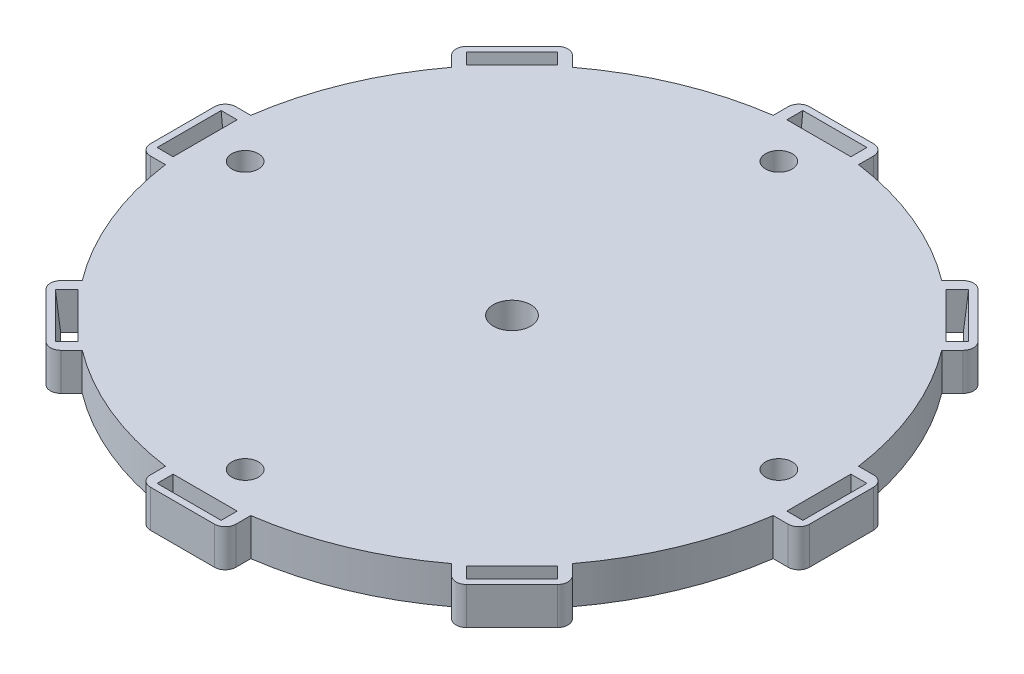
SolidWorks part; units mm, degrees
ref_plane "Front Plane" through (0, 0, 0) normal (0, 0, 1) x (1, 0, 0)
ref_plane "Top Plane" through (0, 0, 0) normal (0, 1, 0) x (1, 0, 0)
ref_plane "Right Plane" through (0, 0, 0) normal (1, 0, 0) x (0, 0, -1)
sketch "Sketch1" plane through (0, 0, 0) normal (0, 1, 0) x (1, 0, 0)
  line L0 (-8, 56.9408) -> (-8, 59.7408)
  line L1 (0, 57.5) -> (0, -57.5) construction
  line L2 (8, 56.9408) -> (8, 59.7408)
  line L3 (-6, 61.7408) -> (6, 61.7408)
  line L4 (39.4147, 47.8999) -> (47.8999, 39.4147)
  line L9 (34.6063, 45.9201) -> (36.5862, 47.8999)
  line L10 (45.9201, 34.6063) -> (47.8999, 36.5862)
  line L15 (61.7408, 6) -> (61.7408, -6)
  line L16 (56.9408, 8) -> (59.7408, 8)
  line L17 (56.9408, -8) -> (59.7408, -8)
  line L22 (47.8999, -39.4147) -> (39.4147, -47.8999)
  line L23 (45.9201, -34.6063) -> (47.8999, -36.5862)
  line L24 (34.6063, -45.9201) -> (36.5862, -47.8999)
  line L29 (6, -61.7408) -> (-6, -61.7408)
  line L30 (8, -56.9408) -> (8, -59.7408)
  line L31 (-8, -56.9408) -> (-8, -59.7408)
  line L36 (-39.4147, -47.8999) -> (-47.8999, -39.4147)
  line L37 (-34.6063, -45.9201) -> (-36.5862, -47.8999)
  line L38 (-45.9201, -34.6063) -> (-47.8999, -36.5862)
  line L43 (-61.7408, -6) -> (-61.7408, 6)
  line L44 (-56.9408, -8) -> (-59.7408, -8)
  line L45 (-56.9408, 8) -> (-59.7408, 8)
  line L50 (-47.8999, 39.4147) -> (-39.4147, 47.8999)
  line L51 (-45.9201, 34.6063) -> (-47.8999, 36.5862)
  line L52 (-34.6063, 45.9201) -> (-36.5862, 47.8999)
  arc A0 (-8, 56.9408) -> (-34.6063, 45.9201) centre (0, 0) ccw
  arc A1 (6, 61.7408) -> (8, 59.7408) centre (6, 59.7408) cw
  arc A2 (-6, 61.7408) -> (-8, 59.7408) centre (-6, 59.7408) ccw
  arc A3 (39.4147, 47.8999) -> (36.5862, 47.8999) centre (38.0005, 46.4857) ccw
  arc A4 (47.8999, 39.4147) -> (47.8999, 36.5862) centre (46.4857, 38.0005) cw
  arc A5 (61.7408, 6) -> (59.7408, 8) centre (59.7408, 6) ccw
  arc A6 (61.7408, -6) -> (59.7408, -8) centre (59.7408, -6) cw
  arc A7 (47.8999, -39.4147) -> (47.8999, -36.5862) centre (46.4857, -38.0005) ccw
  arc A8 (39.4147, -47.8999) -> (36.5862, -47.8999) centre (38.0005, -46.4857) cw
  arc A9 (6, -61.7408) -> (8, -59.7408) centre (6, -59.7408) ccw
  arc A10 (-6, -61.7408) -> (-8, -59.7408) centre (-6, -59.7408) cw
  arc A11 (-39.4147, -47.8999) -> (-36.5862, -47.8999) centre (-38.0005, -46.4857) ccw
  arc A12 (-47.8999, -39.4147) -> (-47.8999, -36.5862) centre (-46.4857, -38.0005) cw
  arc A13 (-61.7408, -6) -> (-59.7408, -8) centre (-59.7408, -6) ccw
  arc A14 (-61.7408, 6) -> (-59.7408, 8) centre (-59.7408, 6) cw
  arc A15 (-47.8999, 39.4147) -> (-47.8999, 36.5862) centre (-46.4857, 38.0005) ccw
  arc A16 (-39.4147, 47.8999) -> (-36.5862, 47.8999) centre (-38.0005, 46.4857) cw
  arc A17 (-45.9201, 34.6063) -> (-56.9408, 8) centre (0, 0) ccw
  arc A18 (-56.9408, -8) -> (-45.9201, -34.6063) centre (0, 0) ccw
  arc A19 (34.6063, 45.9201) -> (8, 56.9408) centre (0, 0) ccw
  arc A20 (-34.6063, -45.9201) -> (-8, -56.9408) centre (0, 0) ccw
  arc A21 (8, -56.9408) -> (34.6063, -45.9201) centre (0, 0) ccw
  arc A22 (45.9201, -34.6063) -> (56.9408, -8) centre (0, 0) ccw
  arc A23 (56.9408, 8) -> (45.9201, 34.6063) centre (0, 0) ccw
  point P11 (8, 61.7408)
  point P14 (-8, 61.7408)
  point P17 (-8, 58.3408)
  point P98 (0, 0)
  dimension "D1" = 115
  dimension "D2" = 2
  dimension "D3" = 16
  dimension "D4" = 2.8
  dimension "D7" = 8
extrude "Boss-Extrude1" add sketch "Sketch1" along normal blind 7
sketch "Sketch2" plane through (0, 7, 0) normal (0, 1, 0) x (1, 0, 0)
  line L0 (-57.5, 0) -> (57.5, 0) construction
  line L1 (0, 0) -> (0, 10) construction
  line L7 (17, 5) -> (22, 5)
  line L14 (0, 10) -> (29.7122, 10) construction
  line L15 (0, 10) -> (-19.5, 10) construction
  line L17 (17, 5) -> (17, 15)
  line L18 (-22, 15) -> (-17, 15)
  line L19 (-22, 15) -> (-22, 5)
  line L20 (-22, 5) -> (-17, 5)
  line L21 (-17, 15) -> (-17, 5)
  line L22 (-22, 15) -> (-17, 5) construction
  line L23 (-22, 5) -> (-17, 15) construction
  line L24 (17, 15) -> (22, 15)
  line L25 (22, 5) -> (22, 15)
  line L26 (17, 5) -> (22, 15) construction
  line L27 (17, 15) -> (22, 5) construction
  circle A0 centre (0, 0) radius 57.5 construction
  point P8 (19.5, 10)
  dimension "D1" = 10
  dimension "D2" = 17
  dimension "D3" = 17
  dimension "D4" = 10
  dimension "D5" = 5
  dimension "D6" = 10
  dimension "D7" = 5
extrude "Boss-Extrude2" add sketch "Sketch2" along normal blind 95
sketch "Sketch15" plane through (0, 0, 0) normal (0, -1, 0) x (1, 0, 0)
  circle A0 centre (0, 0) radius 3.5
  dimension "D1" = 7
extrude "Cut-Extrude3" cut sketch "Sketch15" along direction (0, 1, 0) on the side against the normal up to surface (7 mm away) contours A0 up to face at (0, 7, 0)
sketch "Sketch16" plane through (0, 0, 0) normal (0, -1, 0) x (1, 0, 0)
  line L1 (-6, 59.8) -> (6, 59.8)
  line L2 (-6, 59.8) -> (-6, 57.5)
  line L3 (-6, 57.5) -> (6, 57.5)
  line L4 (6, 59.8) -> (6, 57.5)
  point P5 (0, 57.5)
  dimension "D1" = 2.3
  dimension "D2" = 12
  dimension "D3" = 57.5
sketch "Sketch17" plane through (0, 7, 0) normal (0, 1, 0) x (1, 0, 0)
  line L0 (-6, -57.5) -> (6, -57.5) construction
  line L1 (-6, -57.5) -> (6, -57.5)
  line L2 (-6, -57.5) -> (-6, -60.5)
  line L3 (-6, -60.5) -> (6, -60.5)
  line L4 (6, -60.5) -> (6, -57.5)
  dimension "D1" = 3
ref_axis "Axis1" through (0, 107.1, 0) along (0, -1, 0)
loft "Cut-Loft2" cut profiles "Sketch16", "Sketch17" connector at (6, 0, 59.8) connector at (6, 7, 60.5)
pattern_circular "CirPattern1" count 8 over 360 about axis through (0, 107.1, 0) along (0, -1, 0) of "Cut-Loft2"
sketch "Sketch18" plane through (-17, 0, 0) normal (1, 0, 0) x (0, 0, -1)
  line L0 (15, 102) -> (15, 7) construction
  line L1 (5, 102) -> (15, 102)
  line L2 (5, 102) -> (5, 97)
  line L3 (5, 97) -> (15, 97)
  line L4 (15, 102) -> (15, 97)
  dimension "D1" = 5
extrude "Boss-Extrude3" add sketch "Sketch18" along normal up to surface (34 mm away) up to face at (17, 54.5, -10)
sketch "Sketch19" plane through (0, 0, -15) normal (0, 0, -1) x (-1, 0, 0)
  line L0 (-17, 93) -> (-11.0447, 92.2688)
  line L1 (-17, 97) -> (-17, 7) construction
  line L4 (-11, 91) -> (-19.8185, 91) construction
  line L5 (-17, 89) -> (-11.0447, 89.7312)
  line L6 (-17, 93) -> (-17, 89)
  arc A1 (-11.0447, 92.2688) -> (-11.0447, 89.7312) centre (-11.2005, 91) cw
  dimension "D1" = 6
  dimension "D4" = 4
  dimension "D2" = 7
  dimension "D3" = 4
extrude "Boss-Extrude4" add sketch "Sketch19" against normal blind 10
fillet "Fillet1" radius 2 2 edges at (17, 93, -10) (17, 89, -10)
fillet "Fillet2" radius 2 4 edges at (-22, 102, -10) (22, 102, -10) (-17, 97, -10) (17, 97, -10)
pattern_linear "LPattern2" count 10 spacing 8 along (0, -1, 0) of "Fillet1", "Boss-Extrude4"
sketch "Sketch20" plane through (0, 7, 0) normal (0, 1, 0) x (1, 0, 0)
  line L0 (0, 0) -> (0, 50) construction
  circle A0 centre (0, 50) radius 2.5
  dimension "D2" = 5
  dimension "D1" = 50
extrude "Cut-Extrude4" cut sketch "Sketch20" against normal blind 10
pattern_circular "CirPattern2" count 4 over 360 about axis through (0, 107.1, 0) along (0, -1, 0) of "Cut-Extrude4"
sketch "Sketch22" plane through (0, 0, -15) normal (0, 0, -1) x (-1, 0, 0)
  line L38 (20, 102) -> (-20, 102)
  line L39 (-22, 100) -> (-22, 7)
  line L40 (-22, 7) -> (-17, 7)
  line L41 (-17, 7) -> (-17, 15.2305)
  line L42 (-15.2437, 17.2156) -> (-11.0447, 17.7312)
  line L43 (-11.0447, 20.2688) -> (-15.2437, 20.7844)
  line L44 (-17, 22.7695) -> (-17, 23.2305)
  line L45 (-15.2437, 25.2156) -> (-11.0447, 25.7312)
  line L46 (-11.0447, 28.2688) -> (-15.2437, 28.7844)
  line L47 (-17, 30.7695) -> (-17, 31.2305)
  line L48 (-15.2437, 33.2156) -> (-11.0447, 33.7312)
  line L49 (-11.0447, 36.2688) -> (-15.2437, 36.7844)
  line L50 (-17, 38.7695) -> (-17, 39.2305)
  line L51 (-15.2437, 41.2156) -> (-11.0447, 41.7312)
  line L52 (-11.0447, 44.2688) -> (-15.2437, 44.7844)
  line L53 (-17, 46.7695) -> (-17, 47.2305)
  line L54 (-15.2437, 49.2156) -> (-11.0447, 49.7312)
  line L55 (-11.0447, 52.2688) -> (-15.2437, 52.7844)
  line L56 (-17, 54.7695) -> (-17, 55.2305)
  line L57 (-15.2437, 57.2156) -> (-11.0447, 57.7312)
  line L58 (-11.0447, 60.2688) -> (-15.2437, 60.7844)
  line L59 (-17, 62.7695) -> (-17, 63.2305)
  line L60 (-15.2437, 65.2156) -> (-11.0447, 65.7312)
  line L61 (-11.0447, 68.2688) -> (-15.2437, 68.7844)
  line L62 (-17, 70.7695) -> (-17, 71.2305)
  line L63 (-15.2437, 73.2156) -> (-11.0447, 73.7312)
  line L64 (-11.0447, 76.2688) -> (-15.2437, 76.7844)
  line L65 (-17, 78.7695) -> (-17, 79.2305)
  line L66 (-15.2437, 81.2156) -> (-11.0447, 81.7312)
  line L67 (-11.0447, 84.2688) -> (-15.2437, 84.7844)
  line L68 (-17, 86.7695) -> (-17, 87.2305)
  line L69 (-15.2437, 89.2156) -> (-11.0447, 89.7312)
  line L70 (-11.0447, 92.2688) -> (-15.2437, 92.7844)
  line L71 (-17, 94.7695) -> (-17, 95)
  line L72 (-15, 97) -> (15, 97)
  line L73 (17, 95) -> (17, 7)
  line L74 (17, 7) -> (22, 7)
  line L75 (22, 7) -> (22, 100)
  line L76 (20, 102) -> (-20, 102)
  line L77 (-22, 100) -> (-22, 7)
  line L78 (-22, 7) -> (-17, 7)
  line L79 (-17, 7) -> (-17, 15.2305)
  line L80 (-15.2437, 17.2156) -> (-11.0447, 17.7312)
  line L81 (-11.0447, 20.2688) -> (-15.2437, 20.7844)
  line L82 (-17, 22.7695) -> (-17, 23.2305)
  line L83 (-15.2437, 25.2156) -> (-11.0447, 25.7312)
  line L84 (-11.0447, 28.2688) -> (-15.2437, 28.7844)
  line L85 (-17, 30.7695) -> (-17, 31.2305)
  line L86 (-15.2437, 33.2156) -> (-11.0447, 33.7312)
  line L87 (-11.0447, 36.2688) -> (-15.2437, 36.7844)
  line L88 (-17, 38.7695) -> (-17, 39.2305)
  line L89 (-15.2437, 41.2156) -> (-11.0447, 41.7312)
  line L90 (-11.0447, 44.2688) -> (-15.2437, 44.7844)
  line L91 (-17, 46.7695) -> (-17, 47.2305)
  line L92 (-15.2437, 49.2156) -> (-11.0447, 49.7312)
  line L93 (-11.0447, 52.2688) -> (-15.2437, 52.7844)
  line L94 (-17, 54.7695) -> (-17, 55.2305)
  line L95 (-15.2437, 57.2156) -> (-11.0447, 57.7312)
  line L96 (-11.0447, 60.2688) -> (-15.2437, 60.7844)
  line L97 (-17, 62.7695) -> (-17, 63.2305)
  line L98 (-15.2437, 65.2156) -> (-11.0447, 65.7312)
  line L99 (-11.0447, 68.2688) -> (-15.2437, 68.7844)
  line L100 (-17, 70.7695) -> (-17, 71.2305)
  line L101 (-15.2437, 73.2156) -> (-11.0447, 73.7312)
  line L102 (-11.0447, 76.2688) -> (-15.2437, 76.7844)
  line L103 (-17, 78.7695) -> (-17, 79.2305)
  line L104 (-15.2437, 81.2156) -> (-11.0447, 81.7312)
  line L105 (-11.0447, 84.2688) -> (-15.2437, 84.7844)
  line L106 (-17, 86.7695) -> (-17, 87.2305)
  line L107 (-15.2437, 89.2156) -> (-11.0447, 89.7312)
  line L108 (-11.0447, 92.2688) -> (-15.2437, 92.7844)
  line L109 (-17, 94.7695) -> (-17, 95)
  line L110 (-15, 97) -> (15, 97)
  line L111 (17, 95) -> (17, 7)
  line L112 (17, 7) -> (22, 7)
  line L113 (22, 7) -> (22, 100)
  arc A34 (-20, 102) -> (-22, 100) centre (-20, 100) ccw
  arc A35 (-15.2437, 17.2156) -> (-17, 15.2305) centre (-15, 15.2305) ccw
  arc A36 (-11.0447, 17.7312) -> (-11.0447, 20.2688) centre (-11.2005, 19) ccw
  arc A37 (-17, 22.7695) -> (-15.2437, 20.7844) centre (-15, 22.7695) ccw
  arc A38 (-15.2437, 25.2156) -> (-17, 23.2305) centre (-15, 23.2305) ccw
  arc A39 (-11.0447, 25.7312) -> (-11.0447, 28.2688) centre (-11.2005, 27) ccw
  arc A40 (-17, 30.7695) -> (-15.2437, 28.7844) centre (-15, 30.7695) ccw
  arc A41 (-15.2437, 33.2156) -> (-17, 31.2305) centre (-15, 31.2305) ccw
  arc A42 (-11.0447, 33.7312) -> (-11.0447, 36.2688) centre (-11.2005, 35) ccw
  arc A43 (-17, 38.7695) -> (-15.2437, 36.7844) centre (-15, 38.7695) ccw
  arc A44 (-15.2437, 41.2156) -> (-17, 39.2305) centre (-15, 39.2305) ccw
  arc A45 (-11.0447, 41.7312) -> (-11.0447, 44.2688) centre (-11.2005, 43) ccw
  arc A46 (-17, 46.7695) -> (-15.2437, 44.7844) centre (-15, 46.7695) ccw
  arc A47 (-15.2437, 49.2156) -> (-17, 47.2305) centre (-15, 47.2305) ccw
  arc A48 (-11.0447, 49.7312) -> (-11.0447, 52.2688) centre (-11.2005, 51) ccw
  arc A49 (-17, 54.7695) -> (-15.2437, 52.7844) centre (-15, 54.7695) ccw
  arc A50 (-15.2437, 57.2156) -> (-17, 55.2305) centre (-15, 55.2305) ccw
  arc A51 (-11.0447, 57.7312) -> (-11.0447, 60.2688) centre (-11.2005, 59) ccw
  arc A52 (-17, 62.7695) -> (-15.2437, 60.7844) centre (-15, 62.7695) ccw
  arc A53 (-15.2437, 65.2156) -> (-17, 63.2305) centre (-15, 63.2305) ccw
  arc A54 (-11.0447, 65.7312) -> (-11.0447, 68.2688) centre (-11.2005, 67) ccw
  arc A55 (-17, 70.7695) -> (-15.2437, 68.7844) centre (-15, 70.7695) ccw
  arc A56 (-15.2437, 73.2156) -> (-17, 71.2305) centre (-15, 71.2305) ccw
  arc A57 (-11.0447, 73.7312) -> (-11.0447, 76.2688) centre (-11.2005, 75) ccw
  arc A58 (-17, 78.7695) -> (-15.2437, 76.7844) centre (-15, 78.7695) ccw
  arc A59 (-15.2437, 81.2156) -> (-17, 79.2305) centre (-15, 79.2305) ccw
  arc A60 (-11.0447, 81.7312) -> (-11.0447, 84.2688) centre (-11.2005, 83) ccw
  arc A61 (-17, 86.7695) -> (-15.2437, 84.7844) centre (-15, 86.7695) ccw
  arc A62 (-15.2437, 89.2156) -> (-17, 87.2305) centre (-15, 87.2305) ccw
  arc A63 (-11.0447, 89.7312) -> (-11.0447, 92.2688) centre (-11.2005, 91) ccw
  arc A64 (-17, 94.7695) -> (-15.2437, 92.7844) centre (-15, 94.7695) ccw
  arc A65 (-15, 97) -> (-17, 95) centre (-15, 95) ccw
  arc A66 (17, 95) -> (15, 97) centre (15, 95) ccw
  arc A67 (22, 100) -> (20, 102) centre (20, 100) ccw
  arc A68 (-20, 102) -> (-22, 100) centre (-20, 100) ccw
  arc A69 (-15.2437, 17.2156) -> (-17, 15.2305) centre (-15, 15.2305) ccw
  arc A70 (-11.0447, 17.7312) -> (-11.0447, 20.2688) centre (-11.2005, 19) ccw
  arc A71 (-17, 22.7695) -> (-15.2437, 20.7844) centre (-15, 22.7695) ccw
  arc A72 (-15.2437, 25.2156) -> (-17, 23.2305) centre (-15, 23.2305) ccw
  arc A73 (-11.0447, 25.7312) -> (-11.0447, 28.2688) centre (-11.2005, 27) ccw
  arc A74 (-17, 30.7695) -> (-15.2437, 28.7844) centre (-15, 30.7695) ccw
  arc A75 (-15.2437, 33.2156) -> (-17, 31.2305) centre (-15, 31.2305) ccw
  arc A76 (-11.0447, 33.7312) -> (-11.0447, 36.2688) centre (-11.2005, 35) ccw
  arc A77 (-17, 38.7695) -> (-15.2437, 36.7844) centre (-15, 38.7695) ccw
  arc A78 (-15.2437, 41.2156) -> (-17, 39.2305) centre (-15, 39.2305) ccw
  arc A79 (-11.0447, 41.7312) -> (-11.0447, 44.2688) centre (-11.2005, 43) ccw
  arc A80 (-17, 46.7695) -> (-15.2437, 44.7844) centre (-15, 46.7695) ccw
  arc A81 (-15.2437, 49.2156) -> (-17, 47.2305) centre (-15, 47.2305) ccw
  arc A82 (-11.0447, 49.7312) -> (-11.0447, 52.2688) centre (-11.2005, 51) ccw
  arc A83 (-17, 54.7695) -> (-15.2437, 52.7844) centre (-15, 54.7695) ccw
  arc A84 (-15.2437, 57.2156) -> (-17, 55.2305) centre (-15, 55.2305) ccw
  arc A85 (-11.0447, 57.7312) -> (-11.0447, 60.2688) centre (-11.2005, 59) ccw
  arc A86 (-17, 62.7695) -> (-15.2437, 60.7844) centre (-15, 62.7695) ccw
  arc A87 (-15.2437, 65.2156) -> (-17, 63.2305) centre (-15, 63.2305) ccw
  arc A88 (-11.0447, 65.7312) -> (-11.0447, 68.2688) centre (-11.2005, 67) ccw
  arc A89 (-17, 70.7695) -> (-15.2437, 68.7844) centre (-15, 70.7695) ccw
  arc A90 (-15.2437, 73.2156) -> (-17, 71.2305) centre (-15, 71.2305) ccw
  arc A91 (-11.0447, 73.7312) -> (-11.0447, 76.2688) centre (-11.2005, 75) ccw
  arc A92 (-17, 78.7695) -> (-15.2437, 76.7844) centre (-15, 78.7695) ccw
  arc A93 (-15.2437, 81.2156) -> (-17, 79.2305) centre (-15, 79.2305) ccw
  arc A94 (-11.0447, 81.7312) -> (-11.0447, 84.2688) centre (-11.2005, 83) ccw
  arc A95 (-17, 86.7695) -> (-15.2437, 84.7844) centre (-15, 86.7695) ccw
  arc A96 (-15.2437, 89.2156) -> (-17, 87.2305) centre (-15, 87.2305) ccw
  arc A97 (-11.0447, 89.7312) -> (-11.0447, 92.2688) centre (-11.2005, 91) ccw
  arc A98 (-17, 94.7695) -> (-15.2437, 92.7844) centre (-15, 94.7695) ccw
  arc A99 (-15, 97) -> (-17, 95) centre (-15, 95) ccw
  arc A100 (17, 95) -> (15, 97) centre (15, 95) ccw
  arc A101 (22, 100) -> (20, 102) centre (20, 100) ccw
  dimension "D1" = 0
extrude "Cut-Extrude7" cut sketch "Sketch22" against normal through all
equation "\"85.00.00mm\"=8500"
